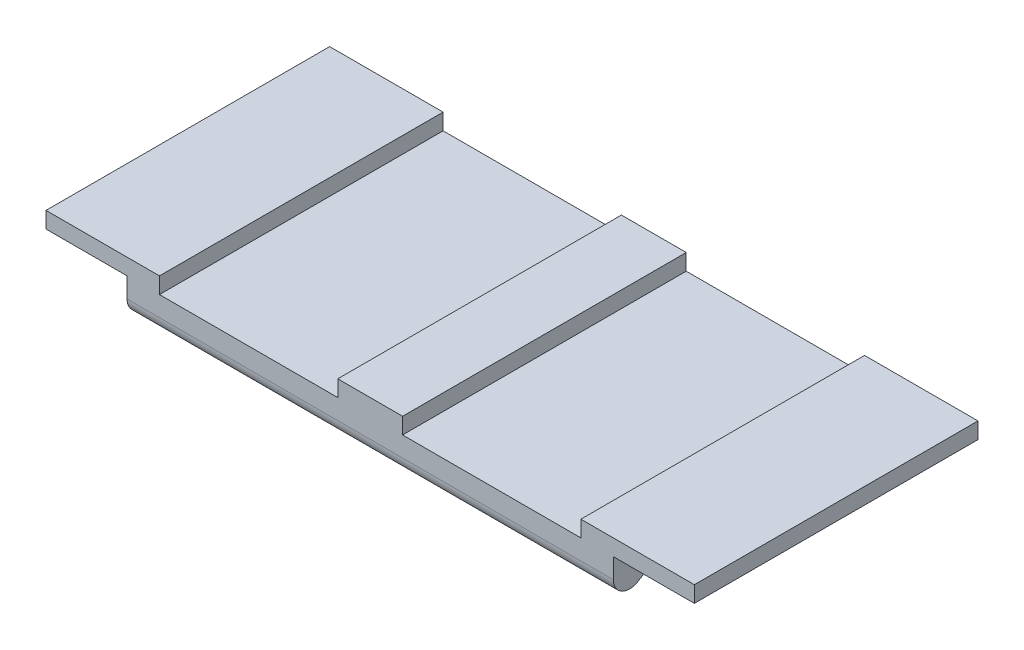
SolidWorks part; units mm, degrees
material "PEI"
ref_plane "Front Plane" through (0, 0, 0) normal (0, 0, 1) x (1, 0, 0)
ref_plane "Top Plane" through (0, 0, 0) normal (0, 1, 0) x (1, 0, 0)
ref_plane "Right Plane" through (0, 0, 0) normal (1, 0, 0) x (0, 0, -1)
sketch "Sketch1" plane through (0, 0, 0) normal (0, 1, 0) x (1, 0, 0)
  line L1 (30, -17.5) -> (-30, -17.5)
  line L2 (30, -17.5) -> (30, 17.5)
  line L3 (30, 17.5) -> (-30, 17.5)
  line L4 (-30, -17.5) -> (-30, 17.5)
  line L5 (30, -17.5) -> (-30, 17.5) construction
  line L6 (30, 17.5) -> (-30, -17.5) construction
  point P0 (0, 0)
  dimension "D1" = 35
  dimension "D2" = 60
extrude "Boss-Extrude1" add sketch "Sketch1" against normal blind 8
sketch "Sketch2" plane through (30, 0, 0) normal (1, 0, 0) x (0, 0, -1)
  line L0 (-17.5, -8) -> (-12.5, -5)
  line L1 (-12.5, -5) -> (12.5, -5)
  line L2 (0, -5) -> (0, -8)
  line L3 (17.5, -8) -> (12.5, -5)
  line L4 (17.5, 0) -> (-17.5, 0)
  line L5 (-17.5, 0) -> (-17.5, -8)
  line L6 (-17.5, -8) -> (17.5, -8)
  line L7 (17.5, -8) -> (17.5, 0)
  line L8 (17.5, 0) -> (-17.5, 0)
  line L9 (-17.5, 0) -> (-17.5, -8)
  line L10 (-17.5, -8) -> (17.5, -8)
  line L11 (17.5, -8) -> (17.5, 0)
  line M7 (-17.5, -8) -> (17.5, -8)
  dimension "D2" = 5
  dimension "D3" = 3
  dimension "D1" = 0
extrude "Cut-Extrude1" cut sketch "Sketch2" against normal through all and the other way through all contours L2 L1 L0 M7 | L3 L1 L2 M7 region at (30, -6.5833, 7.5694) region at (30, -6.5833, -7.5694)
fillet "Fillet1" radius 2 4 edges at (0, -5, 12.5) (0, -5, -12.5) (0, -8, -17.5) (0, -8, 17.5)
sketch "Sketch3" plane through (0, 0, 17.5) normal (0, 0, 1) x (1, 0, 0)
  line L0 (-30, 0) -> (30, 0) construction
  line L1 (-26, 2) -> (-4, 2)
  line L2 (-26, 2) -> (-26, -2)
  line L3 (-26, -2) -> (-4, -2)
  line L4 (-30, 0) -> (-30, -4.4676)
  line L5 (-30, -4.4676) -> (30, -4.4676)
  line L6 (30, -4.4676) -> (30, 0)
  line L7 (30, 0) -> (-30, 0)
  line L8 (-30, 0) -> (-30, -4.4676)
  line L9 (-30, -4.4676) -> (30, -4.4676)
  line L10 (30, -4.4676) -> (30, 0)
  line L11 (30, 0) -> (-30, 0)
  line L12 (-4, 2) -> (-4, -2)
  line L13 (-26, 2) -> (-4, -2) construction
  line L14 (-26, -2) -> (-4, 2) construction
  line L15 (0, 0) -> (0, -4.4676)
  line L16 (26, -2) -> (4, 2) construction
  line L17 (26, 2) -> (4, -2) construction
  line L18 (4, 2) -> (4, -2)
  line L19 (26, -2) -> (4, -2)
  line L20 (26, 2) -> (26, -2)
  line L21 (26, 2) -> (4, 2)
  point P2 (-15, 0)
  point P13 (0, 0)
  point P18 (15, 0)
  dimension "D2" = 22
  dimension "D3" = 4
  dimension "D4" = 15
  dimension "D1" = 0
extrude "Cut-Extrude2" cut sketch "Sketch3" against normal through all contours L12 L11 L2 L3 | L20 L11 L18 L19 region at (-15, -1, 17.5) region at (15, -1, 17.5)
sketch "Sketch5" plane through (-30, 0, 0) normal (-1, 0, 0) x (0, 0, 1)
  line L1 (-17.5, 0) -> (17.5, 0)
  line L2 (-17.5, 0) -> (-17.5, -2)
  line L3 (-17.5, -2) -> (17.5, -2)
  line L4 (17.5, 0) -> (17.5, -2)
  line L6 (-17.5, 0) -> (-17.5, -4.4676)
  line L7 (-14.471, -6.1826) -> (-12.975, -5.285)
  line L8 (-11.946, -5) -> (11.946, -5)
  line L9 (12.975, -5.285) -> (14.471, -6.1826)
  line L10 (17.5, -4.4676) -> (17.5, 0)
  line L11 (17.5, 0) -> (-17.5, 0)
  line L12 (-17.5, 0) -> (-17.5, -4.4676)
  line L13 (-14.471, -6.1826) -> (-12.975, -5.285)
  line L14 (-11.946, -5) -> (11.946, -5)
  line L15 (12.975, -5.285) -> (14.471, -6.1826)
  line L16 (17.5, -4.4676) -> (17.5, 0)
  line L17 (17.5, 0) -> (-17.5, 0)
  arc A4 (-17.5, -4.4676) -> (-14.471, -6.1826) centre (-15.5, -4.4676) ccw
  arc A5 (-11.946, -5) -> (-12.975, -5.285) centre (-11.946, -7) ccw
  arc A6 (12.975, -5.285) -> (11.946, -5) centre (11.946, -7) ccw
  arc A7 (14.471, -6.1826) -> (17.5, -4.4676) centre (15.5, -4.4676) ccw
  arc A8 (-17.5, -4.4676) -> (-14.471, -6.1826) centre (-15.5, -4.4676) ccw
  arc A9 (-11.946, -5) -> (-12.975, -5.285) centre (-11.946, -7) ccw
  arc A10 (12.975, -5.285) -> (11.946, -5) centre (11.946, -7) ccw
  arc A11 (14.471, -6.1826) -> (17.5, -4.4676) centre (15.5, -4.4676) ccw
  line M13 (-17.5, 0) -> (-17.5, -4.4676)
  line M21 (17.5, -4.4676) -> (17.5, 0)
  line M22 (17.5, 0) -> (-17.5, 0)
  dimension "D2" = 2
  dimension "D1" = 0
extrude "Boss-Extrude2" add sketch "Sketch5" along normal blind 10 contours L3 M13 M21 M22 region at (-30, -1, 0)
mirror "Mirror1" about plane through (0, 0, 0) normal (1, 0, 0) of "Boss-Extrude2"
